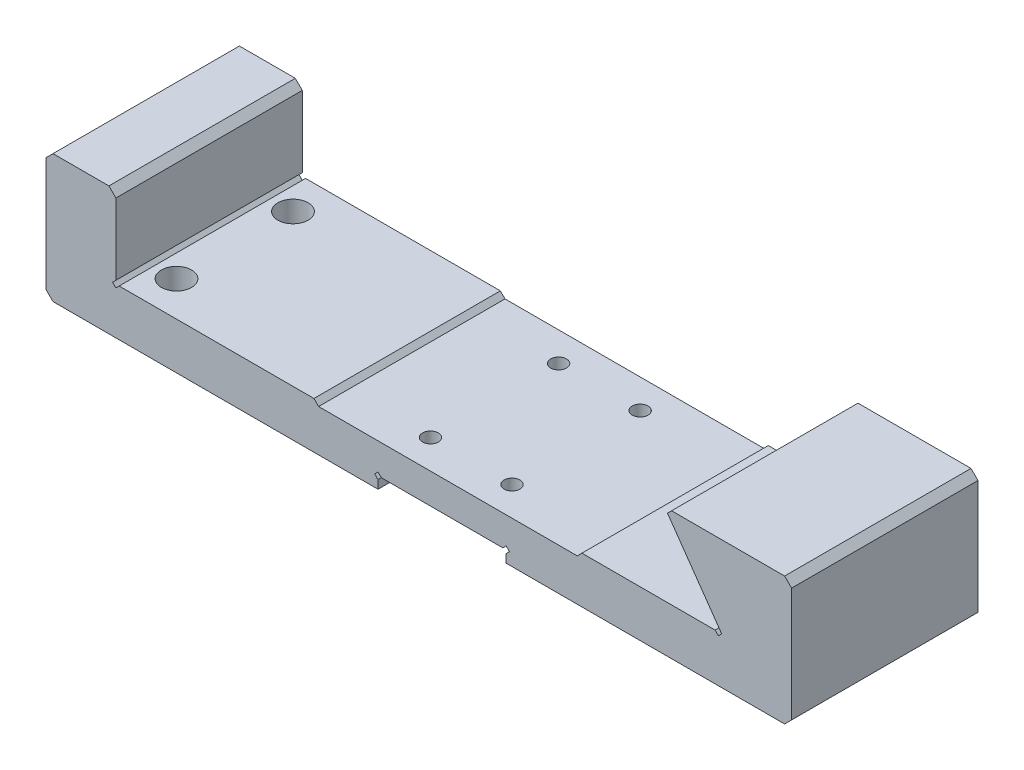
SolidWorks part; units mm, degrees
ref_plane "前视基准面" through (0, 0, 0) normal (0, 0, 1) x (1, 0, 0)
ref_plane "上视基准面" through (0, 0, 0) normal (0, 1, 0) x (1, 0, 0)
ref_plane "右视基准面" through (0, 0, 0) normal (1, 0, 0) x (0, 0, -1)
sketch "草图1" plane through (0, 0, 0) normal (0, 0, 1) x (1, 0, 0)
  line L0 (0, 0) -> (0, 55)
  line L1 (0, -55) -> (0, 55) construction
  line L2 (0, 55) -> (30, 55)
  line L3 (30, 55) -> (30, 20)
  line L4 (30, 20) -> (290, 20)
  line L5 (290, 20) -> (265.4927, 55)
  line L6 (265.4927, 55) -> (320, 55)
  line L7 (320, 55) -> (320, 0)
  line L8 (55, 0) -> (-55, 0) construction
  line L9 (320, 0) -> (0, 0)
  dimension "D1" = 55
  dimension "D2" = 320
  dimension "D3" = 260
  dimension "D4" = 35
  dimension "D5" = 30
  dimension "D6" = 55
extrude "凸台-拉伸1" add sketch "草图1" along normal mid plane 80
sketch "草图2" plane through (0, 0, 40) normal (0, 0, 1) x (1, 0, 0)
  line L0 (115, 20) -> (230, 20)
  line L1 (290, 20) -> (30, 20) construction
  point P4 (172.5, 20)
  dimension "D1" = 60
  dimension "D3" = 85
extrude "切除-拉伸-薄壁1" cut sketch "草图2" against normal blind 80 and the other way through all thin thin type one direction wall 2
chamfer "倒角1" distance 2 angle 45 2 edges at (230, 18, 0) (115, 18, 0)
sketch "草图3" plane through (0, 0, 40) normal (0, 0, 1) x (1, 0, 0)
  line L0 (287.1716, 20) -> (288.5858, 18.5858)
  line L1 (287.1716, 20) -> (288.5858, 21.4142)
  line L2 (288.5858, 18.5858) -> (290, 20)
  line L3 (288.5858, 21.4142) -> (290, 20)
  line L4 (290, 20) -> (230, 20) construction
  line L5 (28.5858, 20) -> (30, 21.4142)
  line L6 (28.5858, 20) -> (30, 18.5858)
  line L7 (30, 21.4142) -> (31.4142, 20)
  line L8 (30, 18.5858) -> (31.4142, 20)
  line L9 (28.5858, 20) -> (31.4142, 20) construction
  line L10 (30, 21.4142) -> (30, 18.5858) construction
  line L11 (115, 20) -> (30, 20) construction
  point P4 (0, 0)
  point P5 (30, 20)
  point P8 (0, 0)
  dimension "D1" = 90
  dimension "D2" = 2
  dimension "D3" = 2
extrude "切除-拉伸1" cut sketch "草图3" against normal blind 80
sketch "草图4" plane through (0, 0, 40) normal (0, 0, 1) x (1, 0, 0)
  line L0 (142.5, 0) -> (197.5, 0)
  line L1 (44, 0) -> (-44, 0) construction
  point P6 (170, 0)
  dimension "D1" = 55
  dimension "D2" = 120
extrude "切除-拉伸-薄壁2" cut sketch "草图4" against normal blind 80 and the other way through all thin thin type one direction reverse wall 5
sketch "草图5" plane through (0, 0, 40) normal (0, 0, 1) x (1, 0, 0)
  line L0 (198.9142, 5) -> (197.5, 6.4142)
  line L1 (198.9142, 5) -> (197.5, 3.5858)
  line L2 (197.5, 6.4142) -> (196.0858, 5)
  line L3 (197.5, 3.5858) -> (196.0858, 5)
  line L4 (198.9142, 5) -> (196.0858, 5) construction
  line L5 (197.5, 6.4142) -> (197.5, 3.5858) construction
  line L6 (142.5, 5) -> (197.5, 5) construction
  point P0 (0, 0)
  point P1 (197.5, 5)
  dimension "D1" = 2
extrude "切除-拉伸2" cut sketch "草图5" against normal blind 80
ref_plane "基准面1" through (170, 0, 0) normal (1, 0, 0) x (0, 0, -1)
mirror "镜向1" about plane through (170, 0, 0) normal (1, 0, 0) of "切除-拉伸2"
sketch "草图6" plane through (0, 5, 0) normal (0, -1, 0) x (1, 0, 0)
  line L0 (170, -1.9722) -> (170, 1.9722) construction
  line L1 (152.5, -27.5) -> (187.5, -27.5) construction
  line L2 (152.5, -27.5) -> (152.5, 27.5) construction
  line L3 (152.5, 27.5) -> (187.5, 27.5) construction
  line L4 (187.5, -27.5) -> (187.5, 27.5) construction
  line L5 (30.25, 0) -> (-30.25, 0) construction
  dimension "D1" = 55
  dimension "D2" = 35
  dimension "D3" = 17.5
  dimension "D4" = 27.5
hole_wizard "M8 螺纹孔1" positions "草图7" profile "草图8" tap size "M8" standard "GB" end condition through all
sketch "草图7" plane through (0, 0, 0) normal (0, -1, 0) x (1, 0, 0)
  line L0 (187.5, -27.5) -> (187.5, 27.5) construction
  line L1 (152.5, 27.5) -> (187.5, 27.5) construction
  line L2 (152.5, -27.5) -> (152.5, 27.5) construction
  point P0 (152.5, 27.5)
  point P3 (187.5, 27.5)
  point P9 (187.5, -27.5)
  point P11 (152.5, -27.5)
sketch "草图8" plane through (152.5, 0, 27.5) normal (1, 0, 0) x (0, 0, -1)
  line L0 (0, 0) -> (0, 55)
  line L1 (0, 55) -> (3.4, 55)
  line L2 (3.4, 55) -> (3.4, 0)
  line L5 (3.4, 0) -> (0, 0)
  line L11 (0, -6.35) -> (0, 107.95) construction
  dimension "通孔螺纹孔钻头直径" = 6.8
  dimension "通孔螺纹孔钻头深度" = 55
cosmetic thread "孔螺纹线1" parameters "D2"=8
cosmetic thread "孔螺纹线2" parameters "D2"=8
cosmetic thread "孔螺纹线3" parameters "D2"=8
cosmetic thread "孔螺纹线4" parameters "D2"=8
sketch "草图9" plane through (0, 20, 0) normal (0, 1, 0) x (1, 0, 0)
  line L0 (41, -25) -> (41, 25) construction
  line L2 (-30.25, 0) -> (30.25, 0) construction
  line L3 (30, -40) -> (30, 40) construction
  point P3 (41, 0)
  point P5 (0, 0)
  dimension "D1" = 50
  dimension "D2" = 11
hole_wizard "孔1" positions "草图10" profile "草图11" legacy end condition through all
sketch "草图10" plane through (0, 20, 0) normal (0, 1, 0) x (1, 0, 0)
  point P0 (41, 25)
  point P5 (41, -25)
  point P8 (0, 0)
  point P9 (41, -25)
sketch "草图11" plane through (41, 20, -25) normal (1, 0, 0) x (0, 0, 1)
  line L0 (0, 0) -> (0, 20)
  line L1 (0, 20) -> (6.5, 20)
  line L2 (6.5, 20) -> (6.5, 0)
  line L3 (6.5, 0) -> (0, 0)
  line L4 (0, 110) -> (0, -10) construction
  dimension "直径" = 13
  dimension "深度" = 20
chamfer "倒角2" distance 3 angle 45 6 edges at (265.4927, 55, 0) (320, 55, 0) (320, 0, 0) (0, 0, 0) (0, 55, 0) (30, 55, 0) first distance on face at (292.7464, 55, 0) first distance on face at (320, 27.5, 0) first distance on face at (258.75, 0, 0) first distance on face at (0, 27.5, 0) first distance on face at (30, 38.2071, 0)
